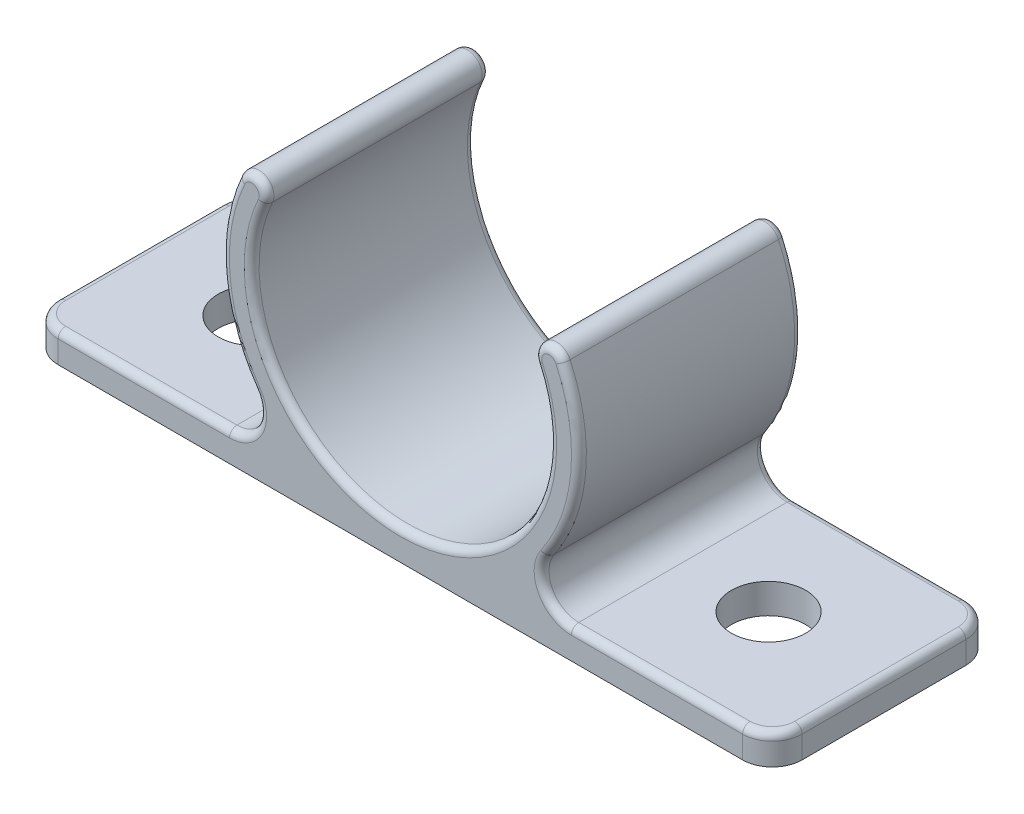
SolidWorks part; units mm, degrees
ref_plane "Front Plane" through (0, 0, 0) normal (0, 0, 1) x (1, 0, 0)
ref_plane "Top Plane" through (0, 0, 0) normal (0, 1, 0) x (1, 0, 0)
ref_plane "Right Plane" through (0, 0, 0) normal (1, 0, 0) x (0, 0, -1)
sketch "Sketch1" plane through (0, 0, 0) normal (0, 0, 1) x (1, 0, 0)
  line L0 (6.6332, -10) -> (25, -10)
  line L1 (-25, -12) -> (25, -12)
  line L2 (-25, -12) -> (-25, -10)
  line L3 (-25, -10) -> (-6.6332, -10)
  line L4 (25, -12) -> (25, -10)
  circle A0 centre (0, 0) radius 10 construction
  arc A1 (9.0909, 4.166) -> (-9.0909, 4.166) centre (0, 0) cw
  arc A2 (10.9091, 4.9992) -> (6.6332, -10) centre (0, 0) cw
  arc A5 (-10.9091, 4.9992) -> (-9.0909, 4.166) centre (-10, 4.5826) cw
  arc A6 (9.0909, 4.166) -> (10.9091, 4.9992) centre (10, 4.5826) cw
  arc A7 (-6.6332, -10) -> (-10.9091, 4.9992) centre (0, 0) cw
  arc A8 (10.9091, 4.9992) -> (-10.9091, 4.9992) centre (0, 0) cw construction
  point P15 (0, -12)
  dimension "D1" = 20
  dimension "D2" = 2
  dimension "D3" = 20
  dimension "D4" = 2
  dimension "D5" = 50
extrude "Boss-Extrude1" add sketch "Sketch1" along normal blind 15
fillet "Fillet1" radius 2 6 edges at (25, -11, 0) (25, -11, 15) (-25, -11, 0) (-25, -11, 15) (-6.6332, -10, 7.5) (6.6332, -10, 7.5)
fillet "Fillet2" radius 0.5 24 edges at (-9.7163, -8.9258, 0) (-11.9522, -1.0699, 0) (-9.5834, 5.4917, 0) (0, -10, 0) (9.5834, 5.4917, 0) (11.9522, -1.0699, 0) (9.7163, -8.9258, 0) (17.2446, -10, 0) (24.4142, -10, 0.5858) (25, -10, 7.5) (24.4142, -10, 14.4142) (17.2446, -10, 15) (9.7163, -8.9258, 15) (11.9522, -1.0699, 15) (9.5834, 5.4917, 15) (0, -10, 15) (-9.5834, 5.4917, 15) (-11.9522, -1.0699, 15) (-9.7163, -8.9258, 15) (-17.2446, -10, 15) (-24.4142, -10, 14.4142) (-25, -10, 7.5) (-24.4142, -10, 0.5858) (-17.2446, -10, 0)
hole_wizard "M6 Tapped Hole1" positions "Sketch2" profile "Sketch3" tap size "M6" standard "ISO" end condition up to next
sketch "Sketch2" plane through (0, -10, 0) normal (0, 1, 0) x (1, 0, 0)
  line L0 (-24.5, -2) -> (-24.5, -13) construction
  line L1 (-11.4891, -0.5) -> (-23, -0.5) construction
  line L2 (23, -0.5) -> (11.4891, -0.5) construction
  line L3 (24.5, -13) -> (24.5, -2) construction
  point P0 (-17.2446, -7.5)
  point P2 (17.2446, -7.5)
  point P7 (-24.5, -7.5)
  point P10 (-17.2446, -0.5)
  point P11 (0, 0)
  point P14 (17.2446, -0.5)
  point P17 (24.5, -7.5)
sketch "Sketch3" plane through (-17.2446, -10, 7.5) normal (1, 0, 0) x (0, 0, 1)
  line L0 (0, 0) -> (0, 2)
  line L1 (0, 2) -> (2.5, 2)
  line L2 (2.5, 2) -> (2.5, 0)
  line L5 (2.5, 0) -> (0, 0)
  line L11 (0, -6.35) -> (0, 107.95) construction
  dimension "Thread Major Dia." = 5
  dimension "Thru Tap Drill Depth" = 2
